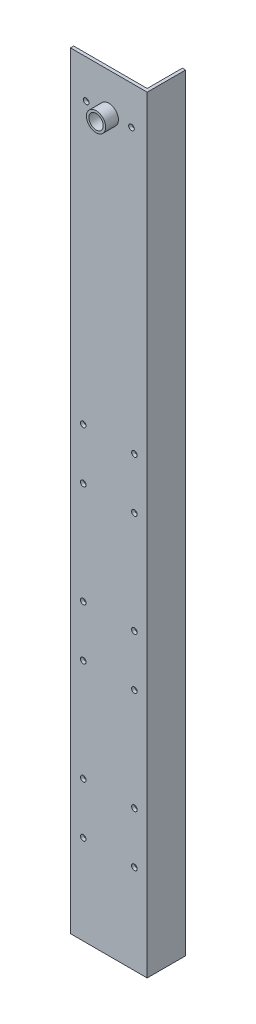
SolidWorks part; units mm, degrees
material "Galvanized Steel"
ref_plane "Front Plane" through (0, 0, 0) normal (0, 0, 1) x (1, 0, 0)
ref_plane "Top Plane" through (0, 0, 0) normal (0, 1, 0) x (1, 0, 0)
ref_plane "Right Plane" through (0, 0, 0) normal (1, 0, 0) x (0, 0, -1)
sketch "Sketch1" plane through (0, 0, 0) normal (0, 1, 0) x (1, 0, 0)
  line L1 (-76.2, -38.1) -> (76.2, -38.1)
  line L2 (-76.2, -38.1) -> (-76.2, 38.1)
  line L3 (-76.2, 38.1) -> (76.2, 38.1)
  line L4 (76.2, -38.1) -> (76.2, 38.1)
  line L5 (-76.2, -38.1) -> (76.2, 38.1) construction
  line L6 (-76.2, 38.1) -> (76.2, -38.1) construction
  point P0 (0, 0)
  dimension "D1" = 152.4
  dimension "D2" = 76.2
extrude "Boss-Extrude1" add sketch "Sketch1" along normal blind 1524
sketch "Sketch2" plane through (0, 0, 38.1) normal (0, 0, 1) x (1, 0, 0)
  line L1 (76.2, 1524) -> (76.2, 0) construction
  circle A0 centre (0, 1447.8) radius 6.35
  dimension "D1" = 12.7
  dimension "D2" = 1447.8
  dimension "D3" = 76.2
extrude "Cut-Extrude1" cut sketch "Sketch2" against normal up to next
sketch "Sketch4" plane through (0, 0, 38.1) normal (0, 0, 1) x (1, 0, 0)
  circle A0 centre (0, 1447.8) radius 14.2875
  circle A1 centre (0, 1447.8) radius 19.05
  dimension "D1" = 38.1
  dimension "D2" = 28.575
extrude "Boss-Extrude2" add sketch "Sketch4" along normal blind 25.4
sketch "Sketch5" plane through (0, 1524, 0) normal (0, 1, 0) x (1, 0, 0)
  line L8 (69.85, 31.75) -> (69.85, 38.1)
  line L9 (76.2, 38.1) -> (-76.2, 38.1) construction
  line L10 (69.85, 38.1) -> (-76.2, 38.1)
  line L11 (-76.2, 38.1) -> (-76.2, -31.75)
  line L12 (69.85, -31.75) -> (69.85, 31.75)
  line L13 (69.85, 31.75) -> (-69.85, 31.75)
  line L14 (-69.85, 31.75) -> (-69.85, -31.75)
  line L15 (-69.85, -31.75) -> (69.85, -31.75)
  line L16 (69.85, -31.75) -> (69.85, 31.75)
  line L19 (-69.85, -31.75) -> (69.85, -31.75)
  line L20 (-76.2, 38.1) -> (-76.2, -38.1) construction
  line L21 (-76.2, -31.75) -> (-69.85, -31.75)
  dimension "D1" = 6.35
extrude "Cut-Extrude2" cut sketch "Sketch5" against normal up to next
sketch "Sketch6" plane through (0, 0, 0) normal (0, -1, 0) x (1, 0, 0)
  line L1 (76.2, -38.1) -> (-76.2, -38.1)
  line L2 (76.2, -38.1) -> (76.2, 38.1)
  line L3 (76.2, 38.1) -> (-76.2, 38.1)
  line L4 (-76.2, -38.1) -> (-76.2, 38.1)
extrude "Boss-Extrude3" add sketch "Sketch6" against normal blind 6.35
sketch "Sketch7" plane through (0, 0, 31.75) normal (0, 0, -1) x (-1, 0, 0)
  line L0 (76.2, 1524) -> (-69.85, 1524) construction
  line L1 (-76.2, 0) -> (76.2, 0) construction
  circle A0 centre (-45.0453, 1447.8) radius 5.5562
  circle A1 centre (45.0453, 1447.8) radius 5.5562
  dimension "D2" = 11.1125
  dimension "D3" = 11.1125
  dimension "D1" = 90.0906
  dimension "D4" = 76.2
  dimension "D5" = 1447.8
extrude "Cut-Extrude3" cut sketch "Sketch7" against normal up to next
sketch "Sketch8" plane through (0, 0, 38.1) normal (0, 0, 1) x (1, 0, 0)
  line L0 (-76.2, 1524) -> (-76.2, 0) construction
  line L1 (-76.2, 0) -> (76.2, 0) construction
  line L2 (76.2, 1524) -> (76.2, 0) construction
  circle A0 centre (-50.8, 177.8) radius 5.5562
  circle A1 centre (50.8, 177.8) radius 5.5562
  circle A2 centre (50.8, 279.4) radius 5.5563
  circle A3 centre (-50.8, 279.4) radius 5.5563
  circle A4 centre (50.8, 482.6) radius 5.5563
  circle A5 centre (50.8, 584.2) radius 5.5563
  circle A6 centre (-50.8, 584.2) radius 5.5563
  circle A7 centre (-50.8, 482.6) radius 5.5563
  circle A8 centre (-50.8, 889) radius 5.5563
  circle A9 centre (-50.8, 787.4) radius 5.5563
  circle A10 centre (50.8, 787.4) radius 5.5563
  circle A11 centre (50.8, 889) radius 5.5563
  dimension "D1" = 11.1125
  dimension "D6" = 11.1125
  dimension "D11" = 11.1125
  dimension "D13" = 101.6
  dimension "D14" = 101.6
  dimension "D2" = 25.4
  dimension "D3" = 177.8
  dimension "D4" = 101.6
  dimension "D5" = 101.6
  dimension "D7" = 482.6
  dimension "D8" = 101.6
  dimension "D9" = 787.4
  dimension "D10" = 101.6
  dimension "D12" = 25.4
extrude "Cut-Extrude4" cut sketch "Sketch8" against normal up to next
